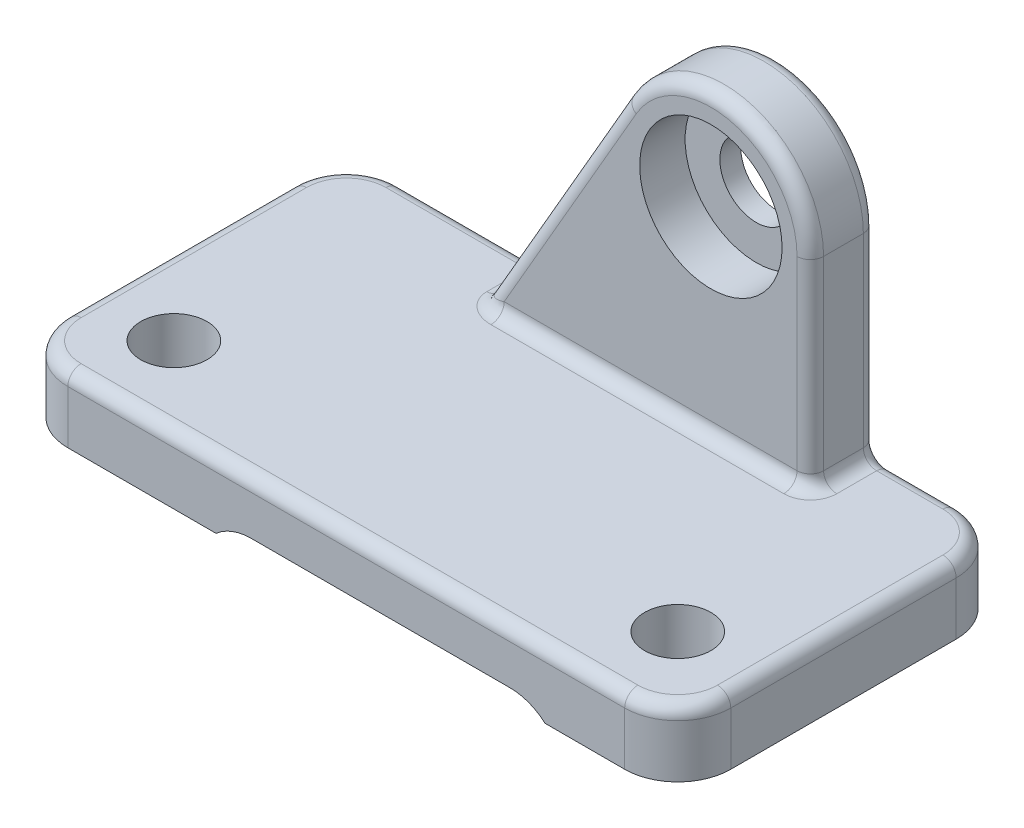
SolidWorks part; units mm, degrees
ref_plane "Front" through (0, 0, 0) normal (0, 0, 1) x (1, 0, 0)
ref_plane "Top" through (0, 0, 0) normal (0, 1, 0) x (1, 0, 0)
ref_plane "Right" through (0, 0, 0) normal (1, 0, 0) x (0, 0, -1)
sketch "Sketch2" plane through (0, 0, 0) normal (0, 1, 0) x (1, 0, 0)
  line L1 (0, 0) -> (100, 0)
  line L2 (0, 0) -> (0, 50)
  line L3 (0, 50) -> (100, 50)
  line L4 (100, 0) -> (100, 50)
  dimension "D1" = 100
  dimension "D2" = 50
extrude "Base" add sketch "Sketch2" along normal blind 10
sketch "Sketch3" plane through (0, 0, -50) normal (0, 0, -1) x (-1, 0, 0)
  line L0 (-80, 10) -> (-80, 40)
  line L1 (-100, 10) -> (0, 10) construction
  line L2 (-52.0096, 47.5) -> (-30.359, 10)
  line L3 (-30.359, 10) -> (-80, 10)
  line L4 (-100, 10) -> (-100, 0) construction
  arc A0 (-80, 40) -> (-52.0096, 47.5) centre (-65, 40) cw
  dimension "D2" = 15
  dimension "D1" = 30
  dimension "D3" = 60
  dimension "D4" = 20
extrude "TopBoss" add sketch "Sketch3" against normal blind 10
sketch "Sketch4" plane through (0, 0, 0) normal (0, 0, 1) x (1, 0, 0)
  line L0 (0, 0) -> (100, 0) construction
  line L1 (30.359, 0) -> (80, 0)
  line L2 (30.359, 0) -> (30.359, 2)
  line L3 (30.359, 2) -> (80, 2)
  line L4 (80, 0) -> (80, 2)
  dimension "D1" = 2
extrude "BottomCut" cut sketch "Sketch4" against normal through all
hole_wizard "CBORE for M10 Hex Head Bolt1" positions "Sketch6" profile "Sketch7" counterbore size "M10" standard "ANSI Metric" end condition through all
sketch "Sketch6" plane through (0, 0, -40) normal (0, 0, 1) x (1, 0, 0)
  point P0 (65, 40)
sketch "Sketch7" plane through (65, 40, -40) normal (1, 0, 0) x (0, -1, 0)
  line L0 (0, 0) -> (0, 10)
  line L1 (0, 10) -> (5.5, 10)
  line L3 (5.5, 10) -> (5.5, 6.85)
  line L4 (5.5, 6.85) -> (10.74, 6.85)
  line L5 (10.74, 6.85) -> (10.74, 0)
  line L7 (10.74, 0) -> (0, 0)
  line L11 (0, -6.35) -> (0, 107.95) construction
  dimension "Thru Hole Dia." = 11
  dimension "Thru Hole Depth" = 10
  dimension "C'Bore Dia." = 21.48
  dimension "C'Bore Depth" = 6.85
hole_wizard "Ø10.0 (10) Diameter Hole1" positions "Sketch8" profile "Sketch10" hole size "Ø10.0" standard "ANSI Metric" end condition through all
sketch "Sketch8" plane through (0, 10, 0) normal (0, 1, 0) x (1, 0, 0)
  line L0 (0, 50) -> (0, 0) construction
  line L1 (0, 0) -> (100, 0) construction
  line L2 (100, 0) -> (100, 50) construction
  point P0 (12, 12)
  point P2 (88, 12)
  dimension "D1" = 12
  dimension "D2" = 12
  dimension "D3" = 12
  dimension "D4" = 12
sketch "Sketch10" plane through (12, 10, -12) normal (1, 0, 0) x (0, 0, 1)
  line L0 (0, 0) -> (0, 10)
  line L1 (0, 10) -> (5, 10)
  line L2 (5, 10) -> (5, 0)
  line L5 (5, 0) -> (0, 0)
  line L11 (0, -6.35) -> (0, 107.95) construction
  dimension "Thru Hole Dia." = 10
  dimension "Thru Hole Depth" = 10
fillet "Fillet1" radius 8 6 edges at (80, 2, -25) (30.359, 2, -25) (100, 5, 0) (100, 5, -50) (0, 5, -50) (0, 5, 0)
fillet "Fillet2" radius 2 18 edges at (41.1843, 28.75, -50) (80, 25, -50) (41.1843, 28.75, -40) (80, 25, -40) (68.8823, 54.4889, -50) (68.8823, 54.4889, -40) (2.3431, 10, -2.3431) (50, 10, 0) (0, 10, -25) (97.6569, 10, -2.3431) (2.3431, 10, -47.6569) (100, 10, -25) (19.1795, 10, -50) (97.6569, 10, -47.6569) (30.359, 10, -45) (86, 10, -50) (55.1795, 10, -40) (80, 10, -45)
